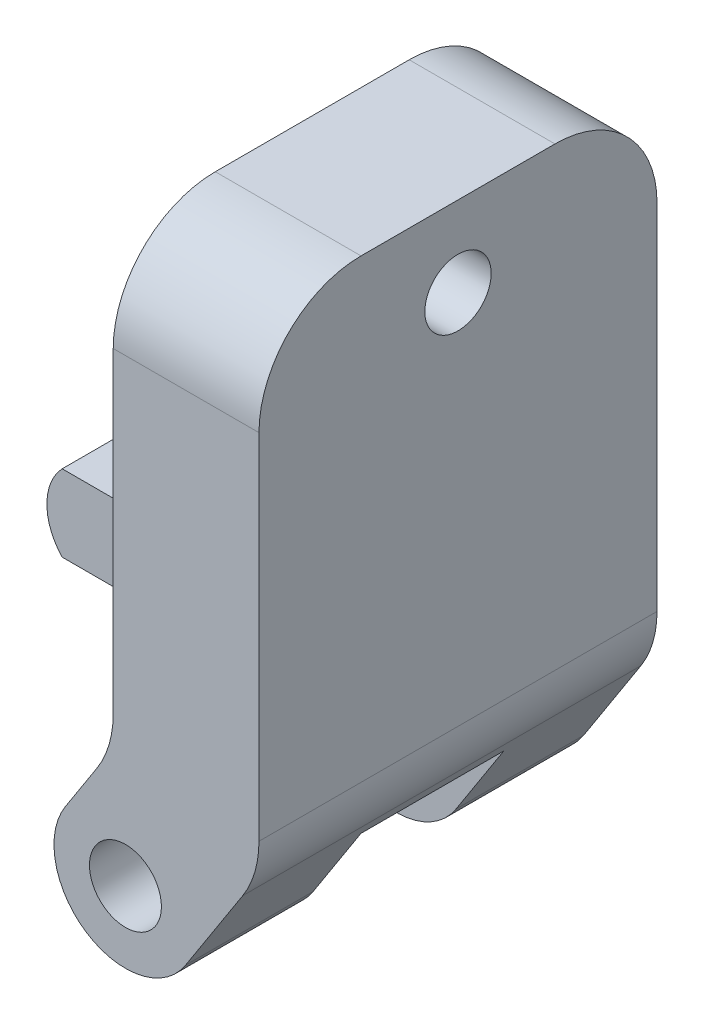
SolidWorks part; units mm, degrees
ref_plane "Front Plane" through (0, 0, 0) normal (0, 0, 1) x (1, 0, 0)
ref_plane "Top Plane" through (0, 0, 0) normal (0, 1, 0) x (1, 0, 0)
ref_plane "Right Plane" through (0, 0, 0) normal (1, 0, 0) x (0, 0, -1)
sketch "Sketch2" plane through (0, 0, 0) normal (0, 0, 1) x (1, 0, 0)
  line L0 (21.6446, -14.3931) -> (25.302, -8.7145)
  line L1 (25.302, -8.7145) -> (25.302, 15.4724)
  line L2 (25.302, 15.4724) -> (18.0472, 15.4724)
  line L3 (18.0472, 15.4724) -> (18.0472, -6.844)
  line L4 (18.0472, -6.844) -> (15.6654, -10.5421)
  arc A0 (15.6654, -10.5421) -> (21.6446, -14.3931) centre (18.655, -12.4676) ccw
  circle A1 centre (9.939, 0) radius 2.5 construction
  dimension "D1" = 5
  dimension "D2" = 7.112
  dimension "D3" = 27.94
extrude "Boss-Extrude1" add sketch "Sketch2" along normal blind 6.35
sketch "Sketch3" plane through (0, 0, 0) normal (0, 0, -1) x (-1, 0, 0)
  line L1 (-18.0472, -6.844) -> (-24.0264, -10.695)
  line L5 (-25.302, 15.4724) -> (-25.302, -8.7145)
  line L6 (-25.302, -8.7145) -> (-21.6446, -14.3931)
  line L7 (-15.6654, -10.5421) -> (-18.0472, -6.844)
  line L8 (-18.0472, -6.844) -> (-18.0472, 15.4724)
  line L9 (-18.0472, 15.4724) -> (-25.302, 15.4724)
  line L10 (-25.302, 15.4724) -> (-25.302, -8.7145)
  line L11 (-25.302, -8.7145) -> (-24.0264, -10.695)
  line L13 (-18.0472, -6.844) -> (-18.0472, 15.4724)
  line L14 (-18.0472, 15.4724) -> (-25.302, 15.4724)
  arc A1 (-21.6446, -14.3931) -> (-15.6654, -10.5421) centre (-18.655, -12.4676) ccw
  dimension "D1" = 0
extrude "Boss-Extrude2" add sketch "Sketch3" along normal blind 7.112
sketch "Sketch4" plane through (0, 0, -7.112) normal (0, 0, -1) x (-1, 0, 0)
  line L5 (-25.302, 15.4724) -> (-25.302, -8.7145)
  line L6 (-18.0472, 15.4724) -> (-25.302, 15.4724)
  line L7 (-18.0472, -6.844) -> (-18.0472, 15.4724)
  line L8 (-15.6654, -10.5421) -> (-18.0472, -6.844)
  line L9 (-25.302, -8.7145) -> (-21.6446, -14.3931)
  line L10 (-25.302, 15.4724) -> (-25.302, -8.7145)
  line L11 (-18.0472, 15.4724) -> (-25.302, 15.4724)
  line L12 (-18.0472, -6.844) -> (-18.0472, 15.4724)
  line L13 (-15.6654, -10.5421) -> (-18.0472, -6.844)
  line L14 (-25.302, -8.7145) -> (-21.6446, -14.3931)
  arc A1 (-21.6446, -14.3931) -> (-15.6654, -10.5421) centre (-18.655, -12.4676) ccw
  arc A2 (-21.6446, -14.3931) -> (-15.6654, -10.5421) centre (-18.655, -12.4676) ccw
  dimension "D1" = 0
extrude "Boss-Extrude3" add sketch "Sketch4" along normal blind 6.35
sketch "Sketch5" plane through (0, 0, 6.35) normal (0, 0, 1) x (1, 0, 0)
  circle A0 centre (18.655, -12.4676) radius 1.7907
  dimension "D1" = 3.5814
extrude "Cut-Extrude1" cut sketch "Sketch5" against normal up to next
sketch "Sketch6" plane through (0, 0, -13.462) normal (0, 0, -1) x (-1, 0, 0)
  circle A0 centre (-18.655, -12.4676) radius 1.524
  dimension "D1" = 3.048
extrude "Cut-Extrude2" cut sketch "Sketch6" against normal up to next
sketch "Sketch7" plane through (25.302, 0, 0) normal (1, 0, 0) x (0, 0, -1)
  line L0 (3.556, 15.4724) -> (3.556, 2.1155) construction
  line L1 (-6.35, 15.4724) -> (13.462, 15.4724) construction
  circle A0 centre (3.556, 11.4795) radius 1.651
  dimension "D1" = 3.302
  dimension "D2" = 3.9929
extrude "Cut-Extrude3" cut sketch "Sketch7" against normal through all
ref_axis "Axis1" through (18.655, -12.4676, -15.9857) along (0, 0, 1)
sketch "Sketch9" plane through (18.0472, 0, 0) normal (-1, 0, 0) x (0, 0, 1)
  line L0 (6.35, 15.4724) -> (6.35, -6.844) construction
  line L2 (-8.682, -1.9037) -> (4.318, -1.9037)
  line L3 (4.318, -1.9037) -> (4.318, 1.9063)
  line L4 (4.318, 1.9063) -> (-8.682, 1.9063)
  line L6 (4.318, 0.0013) -> (-10.056, 0.0013) construction
  line L7 (-15.9857, -12.4676) -> (6.35, -12.4676) construction
  line L8 (4.318, -1.9037) -> (-8.682, -1.9037) construction
  line L9 (-8.682, 1.9063) -> (4.318, 1.9063) construction
  line L10 (-8.682, -1.9037) -> (-8.682, 1.9063)
  point P9 (-2.182, -1.9037)
  point P14 (-2.869, 0.0013)
  point P16 (-2.182, 1.9063)
  dimension "D1" = 12.4689
  dimension "D2" = 3.81
  dimension "D3" = 13
  dimension "D4" = 2.032
extrude "Boss-Extrude4" add sketch "Sketch9" along normal blind 5.334
sketch "Sketch10" plane through (0, 0, -8.682) normal (0, 0, -1) x (-1, 0, 0)
  line L0 (-12.7132, 1.9063) -> (-18.0472, 1.9063) construction
  line L1 (-12.7132, -1.9037) -> (-18.0472, -1.9037) construction
  line L2 (-12.7132, 1.9063) -> (-12.7132, -1.9037) construction
  line L3 (-13.4752, 1.9063) -> (-13.4752, 3.8626)
  line L4 (-13.4752, 3.8626) -> (-11.788, 3.8626)
  line L5 (-11.788, 3.8626) -> (-11.788, -3.9659)
  line L6 (-11.788, -3.9659) -> (-13.4752, -3.9659)
  line L7 (-13.4752, -3.9659) -> (-13.4752, -1.9037)
  arc A0 (-13.4752, 1.9063) -> (-13.4752, -1.9037) centre (-15.4755, 0.0013) cw
  dimension "D1" = 0.762
  dimension "D2" = 0.762
extrude "Cut-Extrude4" cut sketch "Sketch10" against normal through all
sketch "Sketch11" plane through (18.0472, 0, 0) normal (-1, 0, 0) x (0, 0, 1)
  line L0 (-3.094, 1.9063) -> (-3.094, -1.9037) construction
  line L3 (-8.682, 1.9063) -> (-8.682, -1.9037) construction
  line L4 (-6.015, 4.0194) -> (-0.173, 4.0194)
  line L5 (-6.015, 4.0194) -> (-6.015, -4.0169)
  line L6 (-6.015, -4.0169) -> (-0.173, -4.0169)
  line L7 (-0.173, 4.0194) -> (-0.173, -4.0169)
  line L8 (-6.015, 4.0194) -> (-0.173, -4.0169) construction
  line L9 (-6.015, -4.0169) -> (-0.173, 4.0194) construction
  point P6 (-3.094, 0.0013)
  dimension "D1" = 5.842
  dimension "D2" = 8.0362
  dimension "D3" = 5.588
extrude "Cut-Extrude5" cut sketch "Sketch11" along normal through all
fillet "Fillet2" radius 1.27 8 edges at (18.0472, 1.9063, 2.0725) (18.0472, 0.0013, 4.318) (18.0472, -1.9037, 2.0725) (18.0472, 0.0013, -0.173) (18.0472, 0.0013, -8.682) (18.0472, -1.9037, -7.3485) (18.0472, 1.9063, -7.3485) (18.0472, 0.0013, -6.015)
fillet "Fillet3" radius 5.08 2 edges at (21.6746, 15.4724, -13.462) (21.6746, 15.4724, 6.35)
fillet "Fillet4" radius 5.08 3 edges at (25.302, -8.7145, -3.556) (18.0472, -6.844, 3.175) (18.0472, -6.844, -10.287)
